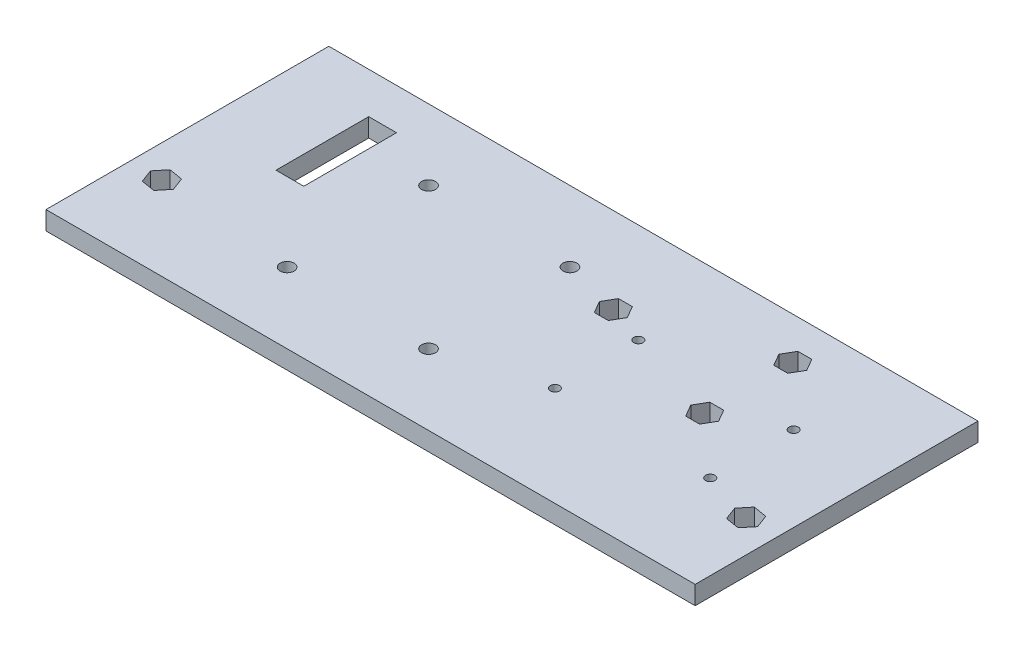
SolidWorks part; units mm, degrees
material "Balsa"
ref_plane "Ebene vorne" through (0, 0, 0) normal (0, 0, 1) x (1, 0, 0)
ref_plane "Ebene oben" through (0, 0, 0) normal (0, 1, 0) x (1, 0, 0)
ref_plane "Ebene rechts" through (0, 0, 0) normal (1, 0, 0) x (0, 0, -1)
sketch "Sketch1" plane through (0, 0, 0) normal (0, 1, 0) x (1, 0, 0)
  line L0 (-24.1206, 0) -> (93.4673, 0) construction
  line L2 (0, 30.5) -> (140, 30.5)
  line L3 (0, 30.5) -> (0, -30.5)
  line L4 (0, -30.5) -> (140, -30.5)
  line L5 (140, 30.5) -> (140, -30.5)
  dimension "D1" = 61
  dimension "D2" = 140
extrude "Boss-Extrude1" add sketch "Sketch1" along normal blind 4
sketch "Sketch2" plane through (0, 4, 0) normal (0, 1, 0) x (1, 0, 0)
  line L1 (17.4497, 21.6501) -> (23.4497, 21.6501)
  line L2 (17.4497, 21.6501) -> (17.4497, 1.6501)
  line L3 (17.4497, 1.6501) -> (23.4497, 1.6501)
  line L4 (23.4497, 21.6501) -> (23.4497, 1.6501)
  dimension "D1" = 20
  dimension "D2" = 6
extrude "Cut-Extrude1" cut sketch "Sketch2" against normal blind 10 contours L4 L3 L2 L1
sketch "Sketch4" plane through (0, 0, 0) normal (0, -1, 0) x (1, 0, 0)
  circle A0 centre (88.25, -9) radius 1
  circle A1 centre (88.25, 9) radius 1
  circle A2 centre (121.75, -9) radius 1
  circle A3 centre (121.75, 9) radius 1
  circle A4 centre (36.75, 15.25) radius 1.5
  circle A5 centre (67.25, 15.25) radius 1.5
  circle A6 centre (67.25, -15.25) radius 1.5
  circle A7 centre (36.75, -15.25) radius 1.5
  dimension "D1" = 3
  dimension "D2" = 2
extrude "Cut-Extrude2" [suppressed] cut sketch "Sketch4" against normal blind 4 contours A5
extrude "Cut-Extrude3" cut sketch "Sketch4<3>" against normal blind 4
sketch "Sketch4<3>" plane through (0, 0, 0) normal (0, -1, 0) x (1, 0, 0) same geometry as "Sketch4"
sketch "Sketch6" plane through (0, 4, 0) normal (0, 1, 0) x (1, 0, 0)
  line L0 (0, 0) -> (140, 0) construction
  line L1 (81.3585, 14.6) -> (78.3563, 14.6)
  line L2 (78.3563, 14.6) -> (76.8552, 12)
  line L3 (76.8552, 12) -> (78.3563, 9.4)
  line L4 (78.3563, 9.4) -> (81.3585, 9.4)
  line L5 (81.3585, 9.4) -> (82.8597, 12)
  line L6 (82.8597, 12) -> (81.3585, 14.6)
  line L7 (140, -30.5) -> (140, 30.5) construction
  line L9 (110.5585, 5.1) -> (107.5563, 5.1)
  line L10 (107.5563, 5.1) -> (106.0552, 2.5)
  line L11 (106.0552, 2.5) -> (107.5563, -0.1)
  line L12 (107.5563, -0.1) -> (110.5585, -0.1)
  line L13 (110.5585, -0.1) -> (112.0597, 2.5)
  line L14 (112.0597, 2.5) -> (110.5585, 5.1)
  line L15 (112.0597, 21.5) -> (110.5585, 24.1)
  line L16 (110.5585, 24.1) -> (107.5563, 24.1)
  line L17 (107.5563, 24.1) -> (106.0552, 21.5)
  line L18 (106.0552, 21.5) -> (107.5563, 18.9)
  line L19 (107.5563, 18.9) -> (110.5585, 18.9)
  line L20 (110.5585, 18.9) -> (112.0597, 21.5)
  circle A0 centre (109.0574, 2.5) radius 2.6 construction
  circle A3 centre (79.8574, 12) radius 2.6 construction
  circle A4 centre (109.0574, 21.5) radius 2.6 construction
  point P9 (79.8574, 9.4)
  dimension "D2" = 5.2
extrude "Cut-Extrude4" cut sketch "Sketch6" against normal blind 34
sketch "Sketch7" plane through (0, 4, 0) normal (0, 1, 0) x (1, 0, 0)
  line L1 (9.9614, -12.9932) -> (8.9078, -10.1819)
  line L2 (8.9078, -10.1819) -> (5.9464, -9.6887)
  line L3 (5.9464, -9.6887) -> (4.0386, -12.0068)
  line L4 (4.0386, -12.0068) -> (5.0922, -14.8181)
  line L5 (5.0922, -14.8181) -> (8.0536, -15.3113)
  line L6 (8.0536, -15.3113) -> (9.9614, -12.9932)
  line L7 (135.9614, -12.9932) -> (134.9078, -10.1819)
  line L8 (134.9078, -10.1819) -> (131.9464, -9.6887)
  line L9 (131.9464, -9.6887) -> (130.0386, -12.0068)
  line L10 (130.0386, -12.0068) -> (131.0922, -14.8181)
  line L11 (131.0922, -14.8181) -> (134.0536, -15.3113)
  line L12 (134.0536, -15.3113) -> (135.9614, -12.9932)
  circle A1 centre (133, -12.5) radius 2.6 construction
  circle A2 centre (7, -12.5) radius 2.6 construction
  dimension "D1" = 5.2
  dimension "D2" = 5.2
extrude "Cut-Extrude5" cut sketch "Sketch7" against normal blind 10
ref_plane "Plane1" through (135.9614, 4, 12.9932) normal (-0.3509, 0, -0.9364) x (-0.9364, 0, 0.3509)
